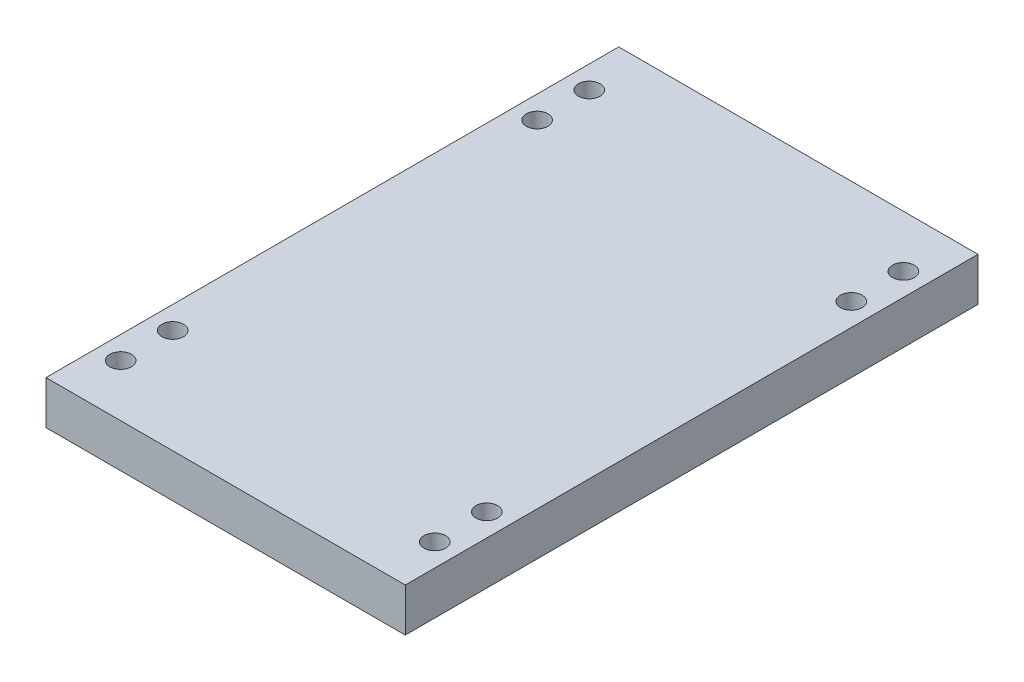
SolidWorks part; units mm, degrees
ref_plane "Front Plane" through (0, 0, 0) normal (0, 0, 1) x (1, 0, 0)
ref_plane "Top Plane" through (0, 0, 0) normal (0, 1, 0) x (1, 0, 0)
ref_plane "Right Plane" through (0, 0, 0) normal (1, 0, 0) x (0, 0, -1)
sketch "Sketch1" plane through (0, 0, 0) normal (0, 1, 0) x (1, 0, 0)
  line L1 (0, 0) -> (-53.594, 0)
  line L2 (0, 0) -> (0, 76.2)
  line L3 (0, 76.2) -> (-53.594, 76.2)
  line L4 (-53.594, 0) -> (-53.594, 76.2)
  dimension "D1" = 76.2
  dimension "D2" = 53.594
extrude "Boss-Extrude1" add sketch "Sketch1" along normal blind 6.35
sketch "Sketch2" plane through (0, 6.35, 0) normal (0, 1, 0) x (1, 0, 0)
  line L0 (0, 0) -> (0, 76.2) construction
  line L1 (-53.594, 0) -> (0, 0) construction
  circle A0 centre (-3.81, 7.62) radius 1.5875
  circle A4 centre (-3.81, 68.58) radius 1.5875
  dimension "D2" = 3.175
  dimension "D1" = 3.81
  dimension "D3" = 7.62
  dimension "D4" = 68.58
extrude "Hole Cuts 1" cut sketch "Sketch2" against normal through all
sketch "Sketch6" plane through (0, 0, 0) normal (0, 0, 1) x (1, 0, 0)
  line L1 (0, 6.35) -> (-53.594, 6.35)
  line L2 (0, 6.35) -> (0, 0)
  line L3 (0, 0) -> (-53.594, 0)
  line L4 (-53.594, 6.35) -> (-53.594, 0)
extrude "Boss-Extrude3" add sketch "Sketch6" along normal blind 7.62
ref_plane "KORAL!!!" through (-26.797, 0, 0) normal (1, 0, 0) x (0, 0, -1)
sketch "Sketch7" plane through (0, 6.35, 0) normal (0, 1, 0) x (1, 0, 0)
  line L0 (0, -7.62) -> (0, 76.2) construction
  line L1 (0, -7.62) -> (-53.594, -7.62) construction
  circle A0 centre (-3.81, 0) radius 1.5875
  circle A1 centre (-3.81, 7.62) radius 1.5875 construction
  circle A2 centre (-3.81, 60.96) radius 1.5875
  point P8 (0, 0)
  dimension "D1" = 3.81
  dimension "D2" = 7.62
  dimension "D3" = 68.58
extrude "Hole Cuts 2" cut sketch "Sketch7" against normal up to next
sketch "Sketch3" plane through (0, 6.35, 0) normal (0, 1, 0) x (1, 0, 0)
  line L1 (0, 76.2) -> (0, -7.62)
  line L2 (-0.508, -7.62) -> (-0.508, 76.2)
  line L3 (0, 76.2) -> (-53.594, 76.2) construction
  line L4 (-0.508, 76.2) -> (0, 76.2)
  line L6 (0, -7.62) -> (-53.594, -7.62) construction
  line L7 (0, -7.62) -> (-0.508, -7.62)
  dimension "D1" = 0.508
extrude "Cut-Extrude2" cut sketch "Sketch3" against normal up to next
mirror "Mirror1" about plane through (-26.797, 0, 0) normal (1, 0, 0) of "Cut-Extrude2", "Hole Cuts 2", "Hole Cuts 1"
